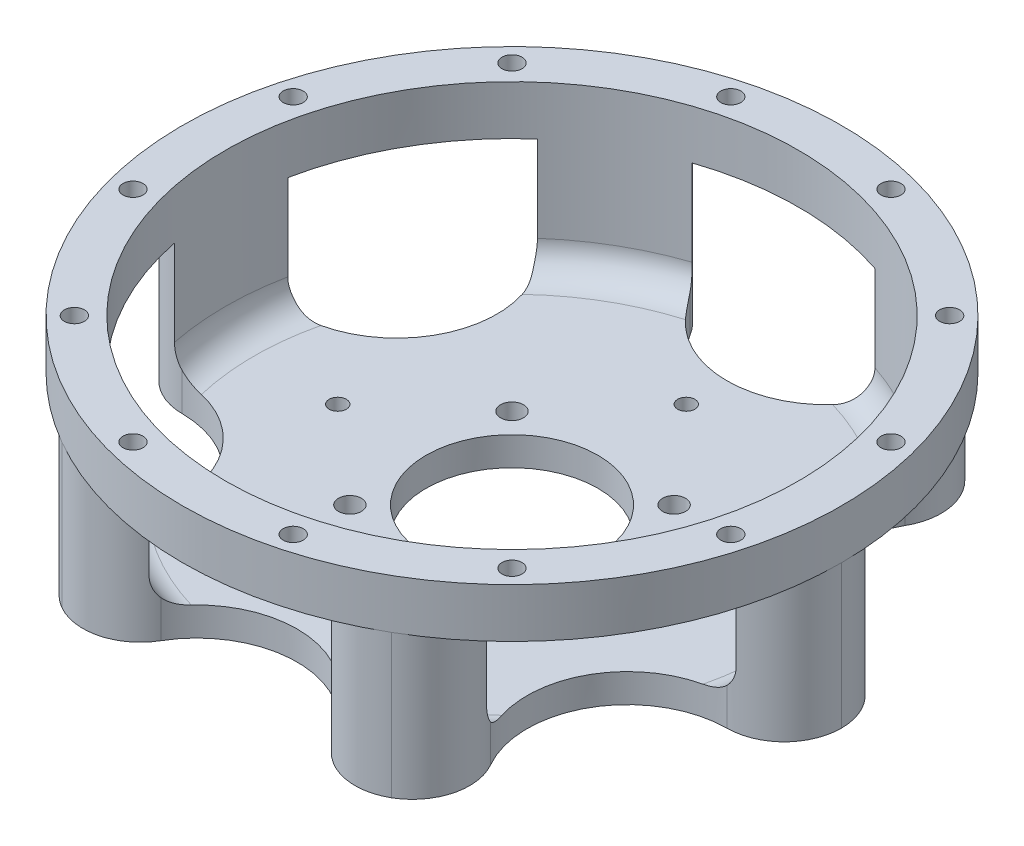
SolidWorks part; units mm, degrees
ref_plane "Front Plane" through (0, 0, 0) normal (0, 0, 1) x (1, 0, 0)
ref_plane "Top Plane" through (0, 0, 0) normal (0, 1, 0) x (1, 0, 0)
ref_plane "Right Plane" through (0, 0, 0) normal (1, 0, 0) x (0, 0, -1)
sketch "Sketch1" plane through (0, 0, 0) normal (0, 1, 0) x (1, 0, 0)
  circle A0 centre (0, 0) radius 57.5
  circle A1 centre (0, 0) radius 55 construction
  point P31 (0, 0)
  dimension "D1" = 115
  dimension "D2" = 110
extrude "Boss-Extrude1" add sketch "Sketch1" along normal blind 33.6
sketch "Sketch2" plane through (0, 33.6, 0) normal (0, 1, 0) x (1, 0, 0)
  circle A0 centre (0, 0) radius 50
  dimension "D1" = 100
extrude "Cut-Extrude1" cut sketch "Sketch2" against normal blind 28.6
sketch "Sketch7" plane through (0, 33.6, 0) normal (0, 1, 0) x (1, 0, 0)
  line L0 (-13.9762, 52.16) -> (0, 0) construction
  line L1 (0, 0) -> (13.9762, 52.16) construction
  line L2 (0, 62.0883) -> (0, -59.7095) construction
  circle A0 centre (0, 0) radius 54 construction
  circle A1 centre (-13.9762, 52.16) radius 1.75
  circle A2 centre (13.9762, 52.16) radius 1.75
  dimension "D1" = 108
  dimension "D4" = 3.5
  dimension "D2" = 15
  dimension "D3" = 15
extrude "Cut-Extrude4" cut sketch "Sketch7" against normal blind 10
fillet "Fillet2" radius 5 1 edges at (0, 5, 50)
sketch "Sketch3" plane through (0, 0, 0) normal (0, -1, 0) x (1, 0, 0)
  line L0 (0, 67.0594) -> (0, -18.0784) construction
  circle A0 centre (0, 0) radius 55 construction
  circle A1 centre (0, 55) radius 17.5
  dimension "D1" = 35
  dimension "D2" = 110
extrude "Cut-Extrude2" cut sketch "Sketch3" against normal blind 25
fillet "Fillet1" radius 10 2 edges at (-17.4985, 12.5, 54.7727) (17.4985, 12.5, 54.7727)
pattern_circular "CirPattern2" count 6 over 360 about axis through (0, 5, 0) along (0, 1, 0) of "Cut-Extrude2", "Fillet1" reverse direction yes
sketch "Sketch5" plane through (0, 0, 0) normal (0, -1, 0) x (1, 0, 0)
  line L0 (-30.4056, 0) -> (0, 30.4056) construction
  line L1 (-30.4056, 0) -> (0, -30.4056) construction
  line L2 (0, 30.4056) -> (30.4056, 0) construction
  line L3 (0, -30.4056) -> (30.4056, 0) construction
  line L4 (-30.4056, 0) -> (0, 0) construction
  line L5 (0, 0) -> (-15.2028, -15.2028) construction
  circle A1 centre (0, 30.4056) radius 1.5
  circle A2 centre (30.4056, 0) radius 1.5
  circle A3 centre (0, -30.4056) radius 1.5
  circle A4 centre (-30.4056, 0) radius 1.5
  circle A5 centre (0, 0) radius 15
  circle A6 centre (0, 0) radius 20 construction
  circle A7 centre (-14.1421, -14.1421) radius 2
  circle A8 centre (-14.1421, 14.1421) radius 2
  circle A9 centre (14.1421, 14.1421) radius 2
  circle A10 centre (14.1421, -14.1421) radius 2
  point P14 (0, 0)
  point P25 (0, 0)
  dimension "D1" = 43
  dimension "D2" = 3
  dimension "D4" = 30
  dimension "D5" = 40
  dimension "D6" = 4
  dimension "D3" = 4
  dimension "D7" = 4
extrude "Cut-Extrude3" cut sketch "Sketch5" against normal blind 25
pattern_circular "CirPattern3" count 6 over 360 about axis through (0, 25, 0) along (0, -1, 0) of "Cut-Extrude4" reverse direction yes
